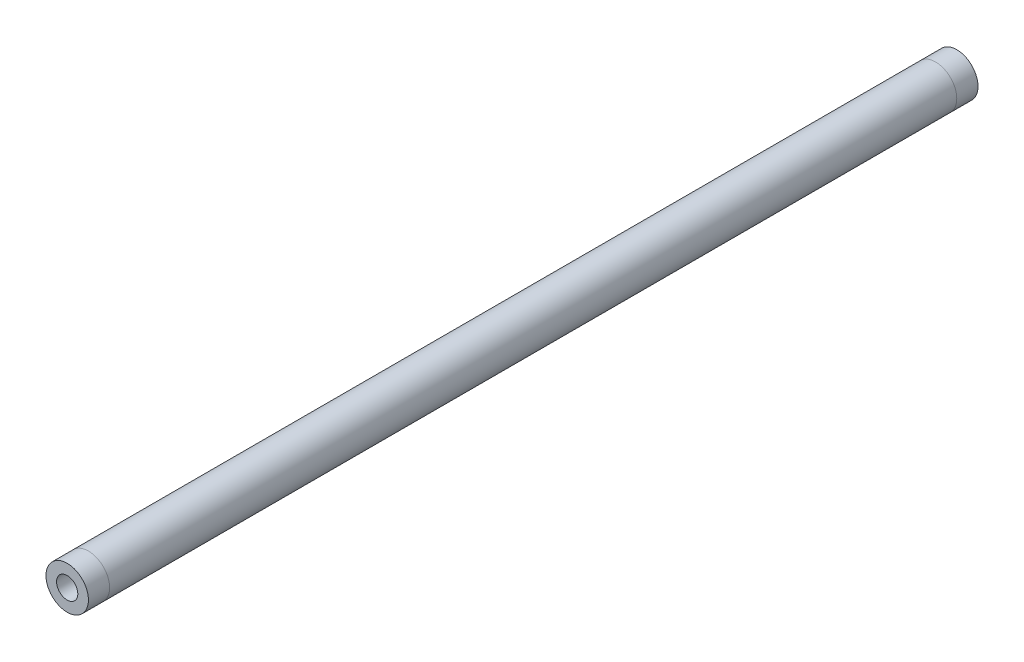
SolidWorks part; units mm, degrees
material "AISI 4130 Steel, annealed at 865C"
ref_plane "Front Plane" through (0, 0, 0) normal (0, 0, 1) x (1, 0, 0)
ref_plane "Top Plane" through (0, 0, 0) normal (0, 1, 0) x (1, 0, 0)
ref_plane "Right Plane" through (0, 0, 0) normal (1, 0, 0) x (0, 0, -1)
sketch "Axis" plane through (0, 0, 0) normal (1, 0, 0) x (0, 0, -1)
  line L0 (0, 0) -> (266.1105, 0) construction
  line L1 (266.1105, 0) -> (259.7605, 0)
  line L2 (266.1105, 0) -> (288.0053, 0) construction
  line L3 (0, 0) -> (-21.8948, 0) construction
  point P4 (0, 0)
  point P5 (266.1105, 0)
  point P6 (259.7605, 0)
  point P8 (288.0053, 0)
  dimension "D1" = 6.35
  dimension "D2" = 21.8948
  dimension "D3" = 21.8948
sketch "Sketch1" plane through (0, 0, 0) normal (0, 0, 1) x (1, 0, 0)
  circle A0 centre (0, 0) radius 6.35
  circle A1 centre (0, 0) radius 4.826
  circle A2 centre (0, 0) radius 3.175
  dimension "D1" = 12.7
  dimension "D2" = 1.524
  dimension "D3" = 6.35
extrude "Threaded insert 1-1" add sketch "Sketch1" against normal blind 6.35 contours A0 A1 | A1 A2 region at (-6.1704, 0, 0) region at (-4.6895, 0, 0)
extrude "Threaded insert 1-2" add sketch "Sketch1<3>" against normal blind 9.525 from surface contours A1 A2 region at (-4.6895, 0, 0) starting at face at (6.35, 0, -6.35)
sketch "Sketch1<3>" plane through (0, 0, 0) normal (0, 0, 1) x (1, 0, 0) same geometry as "Sketch1"
extrude "Tube extrude" add sketch "Sketch1<4>" against normal up to vertex (259.7605 mm away) from surface separate body contours A0 A1 region at (-6.1704, 0, 0) up to point (0, 0, -259.7605) starting at face at (4.826, 0, -6.35)
sketch "Sketch1<4>" plane through (0, 0, 0) normal (0, 0, 1) x (1, 0, 0) same geometry as "Sketch1"
extrude "Threaded insert 2-1" add sketch "Sketch1<6>" along normal blind 9.525 from surface separate body contours A1 A2 region at (-4.6895, 0, 0) starting at face at (4.826, 0, -259.7605)
sketch "Sketch1<6>" plane through (0, 0, 0) normal (0, 0, 1) x (1, 0, 0) same geometry as "Sketch1"
extrude "Threaded insert 2-2" add sketch "Sketch1<9>" against normal blind 6.35 from surface separate body contours A1 A2 | A0 A1 region at (-6.1704, 0, 0) region at (-4.6895, 0, 0) starting at face at (4.826, 0, -259.7605)
sketch "Sketch1<9>" plane through (0, 0, 0) normal (0, 0, 1) x (1, 0, 0) same geometry as "Sketch1"
combine bodies "Combine1" operation type add bodies to combine 106 104
equation "\"Threaded insert outer thickness\"= .25"
equation "\"D1@Threaded insert 1-1\"=\"Threaded insert outer thickness\""
equation "\"D1@Threaded insert 2-2\"=\"Threaded insert outer thickness\""
equation "\"D1@Axis\" = \"Threaded insert outer thickness\""
